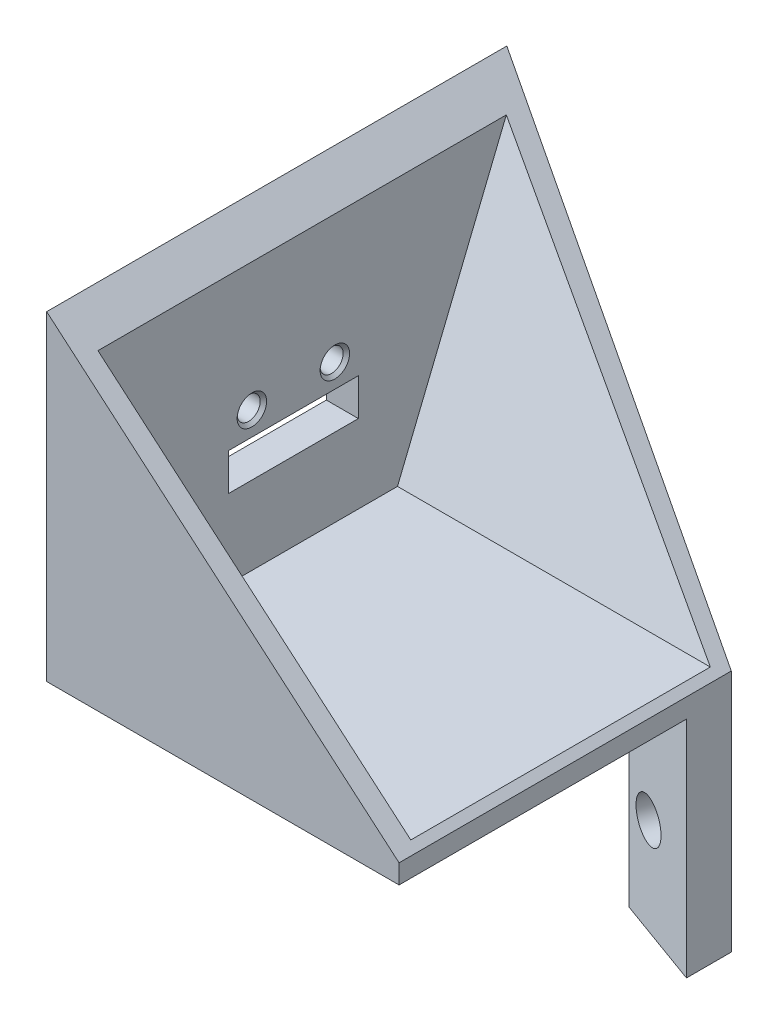
SolidWorks part; units mm, degrees
ref_plane "Front Plane" through (0, 0, 0) normal (0, 0, 1) x (1, 0, 0)
ref_plane "Top Plane" through (0, 0, 0) normal (0, 1, 0) x (1, 0, 0)
ref_plane "Right Plane" through (0, 0, 0) normal (1, 0, 0) x (0, 0, -1)
ref_plane "Plane1" through (0, 1233.8351, 0) normal (0, 1, 0) x (1, 0, 0)
sketch "Sketch2" plane through (0, 1233.8351, 0) normal (0, 1, 0) x (1, 0, 0)
  line L0 (1063.9774, -1311.4767) -> (1423.9774, -1311.4767) construction
  line L1 (1063.9774, -1311.4767) -> (1423.9774, -1311.4767) construction
  line L2 (1423.9774, -1311.4767) -> (1663.9774, -1311.4767) construction
  line L3 (1325.5113, -1311.4767) -> (1325.5113, -951.4767) construction
  line L8 (1325.5113, -956.4767) -> (1325.5113, -1026.4767) construction
  line L9 (1325.5113, -1026.4767) -> (1375.5113, -1026.4767)
  line L10 (1375.5113, -1026.4767) -> (1375.5113, -974.6212)
  line L11 (1375.5113, -974.6212) -> (1325.5113, -956.4767)
  line L12 (1375.5113, -1026.4767) -> (1375.5113, -969.6212) construction
  line L13 (1325.5113, -1026.4767) -> (1320.5113, -1026.4767)
  line L14 (1320.5113, -1026.4767) -> (1320.5113, -956.4767)
  line L15 (1320.5113, -956.4767) -> (1325.5113, -956.4767)
  ellipse E0 centre (1063.9774, -1311.4767) end of major axis (463.9774, -1311.4767) minor radius 400 (1063.9774, -1711.4767) -> (1063.9774, -911.4767) ccw construction
  ellipse E1 centre (1063.9774, -1311.4767) end of major axis (463.9774, -1311.4767) minor radius 400 (1063.9774, -1711.4767) -> (1063.9774, -911.4767) ccw construction
  dimension "D1" = 360
  dimension "D2" = 70
  dimension "D3" = 50
  dimension "D4" = 5
  dimension "D5" = 5
  dimension "D6" = 5
extrude "Boss-Extrude2" add sketch "Sketch2" against normal blind 50 contours L9 L10 L11 L15 L14 L13
sketch "Sketch3" plane through (0, 0, 1026.4767) normal (0, 0, 1) x (1, 0, 0)
  line L0 (1320.5113, 1233.8351) -> (1375.5113, 1186.8351)
  line L1 (1375.5113, 1183.8351) -> (1375.5113, 1233.8351) construction
  line M2 (1375.5113, 1233.8351) -> (1320.5113, 1233.8351)
  line M5 (1375.5113, 1183.8351) -> (1375.5113, 1233.8351)
  dimension "D1" = 3
extrude "Cut-Extrude1" cut sketch "Sketch3" against normal through all and the other way through all contours L0 M2 M5 region at (1357.178, 1218.1684, 1026.4767)
ref_plane "Plane3" through (0, 1233.8351, 0) normal (0, -1, 0) x (-1, 0, 0)
sketch "Sketch6" plane through (0, 1233.8351, 0) normal (0, -1, 0) x (-1, 0, 0)
  line L0 (-1375.5113, -974.6212) -> (-1325.5113, -956.4767) construction
  line L1 (-1375.5113, -974.6212) -> (-1375.5113, -1026.4767) construction
  line L2 (-1320.5113, -1026.4767) -> (-1375.5113, -1026.4767) construction
  line L3 (-1320.5113, -1026.4767) -> (-1320.5113, -956.4767) construction
  line L4 (-1375.5113, -974.6212) -> (-1325.5113, -956.4767) construction
  line L5 (-1375.5113, -974.6212) -> (-1375.5113, -1026.4767) construction
  line L6 (-1320.5113, -1026.4767) -> (-1375.5113, -1026.4767) construction
  line L7 (-1320.5113, -1026.4767) -> (-1320.5113, -956.4767) construction
  line L8 (-1325.5113, -1023.4767) -> (-1372.5113, -1023.4767)
  line L9 (-1372.5113, -1023.4767) -> (-1372.5113, -976.724)
  line L11 (-1325.5113, -976.724) -> (-1325.5113, -1023.4767)
  line L12 (-1372.5113, -976.724) -> (-1325.5113, -976.724)
  dimension "D1" = 3
  dimension "D2" = 5
  dimension "D3" = 3
  dimension "D5" = 3
extrude "Cut-Extrude3" cut sketch "Sketch6" along normal blind 46 contours L11 L9 L8 region at (1349.0113, 1233.8351, 1000.1003)
sketch "Sketch8" plane through (1372.5113, 0, 0) normal (-1, 0, 0) x (0, 0, 1)
  line L4 (976.724, 1189.3987) -> (976.724, 1187.8351)
  line L5 (976.724, 1187.8351) -> (1023.4767, 1187.8351)
  line L6 (1023.4767, 1187.8351) -> (1023.4767, 1189.3987)
  line L7 (1023.4767, 1189.3987) -> (976.724, 1189.3987)
  line L8 (976.724, 1189.3987) -> (976.724, 1187.8351)
  line L9 (976.724, 1187.8351) -> (1023.4767, 1187.8351)
  line L10 (1023.4767, 1187.8351) -> (1023.4767, 1189.3987)
  line L11 (1023.4767, 1189.3987) -> (976.724, 1189.3987)
  dimension "D1" = 0
extrude "Cut-Extrude5" cut sketch "Sketch8" against normal through all
sketch "Sketch7" plane through (1325.5113, 0, 0) normal (1, 0, 0) x (0, 0, -1)
  line L0 (-976.724, 1229.5624) -> (-959.736, 1229.5624)
  line L1 (-976.724, 1229.5624) -> (-976.724, 1187.8351) construction
  line L2 (-976.724, 1229.5624) -> (-976.724, 1187.8351)
  line L3 (-976.724, 1187.8351) -> (-959.736, 1229.5624)
  line L4 (-974.6212, 1186.8351) -> (-956.4767, 1229.5624) construction
  dimension "D1" = 3
extrude "Cut-Extrude4" cut sketch "Sketch7" along normal up to surface (50 mm away) up to face at (1375.5113, 1185.3351, 1000.549)
sketch "Sketch9" plane through (1325.5113, 0, 0) normal (1, 0, 0) x (0, 0, -1)
  line L0 (-956.4767, 1229.5624) -> (-992.9767, 1229.5624) construction
  line L1 (-1023.4767, 1229.5624) -> (-959.736, 1229.5624) construction
  line L2 (-992.9767, 1229.5624) -> (-992.9767, 1187.8351) construction
  line L3 (-976.724, 1187.8351) -> (-1023.4767, 1187.8351) construction
  line L4 (-992.9767, 1209.5424) -> (-999.4517, 1209.5424) construction
  line L5 (-1003.1267, 1198.9674) -> (-982.8267, 1198.9674) construction
  line L7 (-1003.1267, 1205.8574) -> (-982.8267, 1205.8574)
  line L8 (-1003.1267, 1205.8574) -> (-1003.1267, 1200.0574)
  line L9 (-1003.1267, 1200.0574) -> (-982.8267, 1200.0574)
  line L10 (-982.8267, 1205.8574) -> (-982.8267, 1200.0574)
  circle A0 centre (-999.4517, 1209.5424) radius 1.8
  circle A1 centre (-986.5017, 1209.5424) radius 1.8
  dimension "D2" = 3.6
  dimension "D1" = 36.5
  dimension "D3" = 6.475
  dimension "D4" = 20.02
  dimension "D5" = 10.575
  dimension "D6" = 20.3
  dimension "D7" = 10.15
  dimension "D8" = 20.3
  dimension "D9" = 10.15
  dimension "D10" = 5.8
  dimension "D11" = 1.09
extrude "Cut-Extrude6" cut sketch "Sketch9" against normal through all contours A1 | L10 L7 L8 L9 | A0 region at (1325.5113, 1202.9574, 992.9767) region at (1325.5113, 1209.5424, 999.4517) region at (1325.5113, 1209.5424, 986.5017)
sketch "Sketch11" plane through (0, 1183.8351, 0) normal (0, -1, 0) x (1, 0, 0)
  line L0 (1325.5113, 956.4767) -> (1320.5113, 954.6622)
  line L1 (1320.5113, 954.6622) -> (1320.5113, 956.4767)
  line L2 (1375.5113, 974.6212) -> (1375.5113, 981.6212)
  line L3 (1375.5113, 981.6212) -> (1361.411, 976.5044)
  line L4 (1361.411, 976.5044) -> (1361.411, 969.5044)
  line L5 (1375.5113, 1026.4767) -> (1320.5113, 1026.4767)
  line L6 (1320.5113, 1026.4767) -> (1320.5113, 956.4767)
  line L7 (1320.5113, 956.4767) -> (1325.5113, 956.4767)
  line L8 (1325.5113, 956.4767) -> (1375.5113, 974.6212)
  line L9 (1375.5113, 974.6212) -> (1375.5113, 1026.4767)
  line L10 (1375.5113, 1026.4767) -> (1320.5113, 1026.4767) construction
  line L11 (1320.5113, 1026.4767) -> (1320.5113, 956.4767) construction
  line L12 (1320.5113, 956.4767) -> (1325.5113, 956.4767) construction
  line L13 (1325.5113, 956.4767) -> (1375.5113, 974.6212) construction
  line L14 (1375.5113, 974.6212) -> (1375.5113, 1026.4767) construction
  line M12 (1320.5113, 956.4767) -> (1325.5113, 956.4767)
  line M13 (1325.5113, 956.4767) -> (1375.5113, 974.6212)
  line M14 (1375.5113, 974.6212) -> (1375.5113, 1026.4767)
  dimension "D2" = 7
  dimension "D3" = 15
  dimension "D1" = 0
extrude "Boss-Extrude5" add sketch "Sketch11" against normal up to surface (50 mm away) contours L1 L0 M12 region at (1322.178, 1183.8351, 955.8719) up to face at (1343.5113, 1214.1805, 988.1056)
extrude "Boss-Extrude6" add sketch "Sketch11<3>" along normal blind 35 contours L3 L4 M13 M14 region at (1368.4612, 1183.8351, 975.5628)
sketch "Sketch11<3>" plane through (0, 1183.8351, 0) normal (0, -1, 0) x (1, 0, 0) same geometry as "Sketch11"
sketch "Sketch12" plane through (0, 1183.8351, 0) normal (0, -1, 0) x (1, 0, 0)
  line L0 (1320.5113, 1026.4767) -> (1320.5113, 954.6622) construction
  line L1 (1361.411, 969.5044) -> (1320.5113, 954.6622) construction
  line L2 (1320.5113, 1026.4767) -> (1320.5113, 954.6622) construction
  line L3 (1361.411, 969.5044) -> (1320.5113, 954.6622) construction
  line L4 (1320.5113, 954.6622) -> (1320.5113, 961.6622)
  line L5 (1320.5113, 961.6622) -> (1334.6116, 966.7791)
  line L6 (1334.6116, 966.7791) -> (1334.6116, 959.7791)
  line M8 (1320.5113, 1026.4767) -> (1320.5113, 954.6622)
  line M9 (1320.5113, 954.6622) -> (1361.411, 969.5044)
  dimension "D1" = 7
  dimension "D2" = 15
extrude "Boss-Extrude7" add sketch "Sketch12" along normal blind 35 contours L6 L5 M8 M9 region at (1327.5614, 1183.8351, 960.7207)
sketch "Sketch13" plane through (-152.4626, 0, 420.1337) normal (0.3411, 0, -0.94) x (-0.94, 0, -0.3411)
  line L0 (-1617.9725, 1148.8351) -> (-1617.9725, 1183.8351) construction
  line L1 (-1617.9725, 1183.8351) -> (-1610.4725, 1183.8351) construction
  line L2 (-1574.463, 1148.8351) -> (-1574.463, 1183.8351) construction
  line L3 (-1574.463, 1183.8351) -> (-1581.963, 1183.8351) construction
  line L8 (-1566.963, 1233.8351) -> (-1625.4725, 1186.8351)
  line L9 (-1625.4725, 1186.8351) -> (-1625.4725, 1148.8351)
  line L10 (-1625.4725, 1148.8351) -> (-1610.4725, 1148.8351)
  line L11 (-1610.4725, 1148.8351) -> (-1610.4725, 1183.8351)
  line L12 (-1610.4725, 1183.8351) -> (-1581.963, 1183.8351)
  line L13 (-1581.963, 1183.8351) -> (-1581.963, 1148.8351)
  line L14 (-1581.963, 1148.8351) -> (-1566.963, 1148.8351)
  line L15 (-1566.963, 1148.8351) -> (-1566.963, 1233.8351)
  line L16 (-1566.963, 1233.8351) -> (-1625.4725, 1186.8351) construction
  line L17 (-1625.4725, 1186.8351) -> (-1625.4725, 1148.8351) construction
  line L18 (-1625.4725, 1148.8351) -> (-1610.4725, 1148.8351) construction
  line L19 (-1610.4725, 1148.8351) -> (-1610.4725, 1183.8351) construction
  line L20 (-1610.4725, 1183.8351) -> (-1581.963, 1183.8351) construction
  line L21 (-1581.963, 1183.8351) -> (-1581.963, 1148.8351) construction
  line L22 (-1581.963, 1148.8351) -> (-1566.963, 1148.8351) construction
  line L23 (-1566.963, 1148.8351) -> (-1566.963, 1233.8351) construction
  circle A0 centre (-1617.9725, 1163.8351) radius 3.254
  circle A1 centre (-1574.463, 1163.8351) radius 3.254
  dimension "D1" = 6.508
  dimension "D2" = 6.508
  dimension "D4" = 15
  dimension "D5" = 15
  dimension "D3" = 0
extrude "Cut-Extrude7" cut sketch "Sketch13" against normal through all contours A0 | A1 region at (1368.4612, 1163.8351, 972.0628) region at (1327.5614, 1163.8351, 957.2207)
chamfer "Chamfer1" distance 0.5 angle 45 2 edges at (1325.5113, 1209.5424, 997.6517) (1325.5113, 1209.5424, 984.7017)
